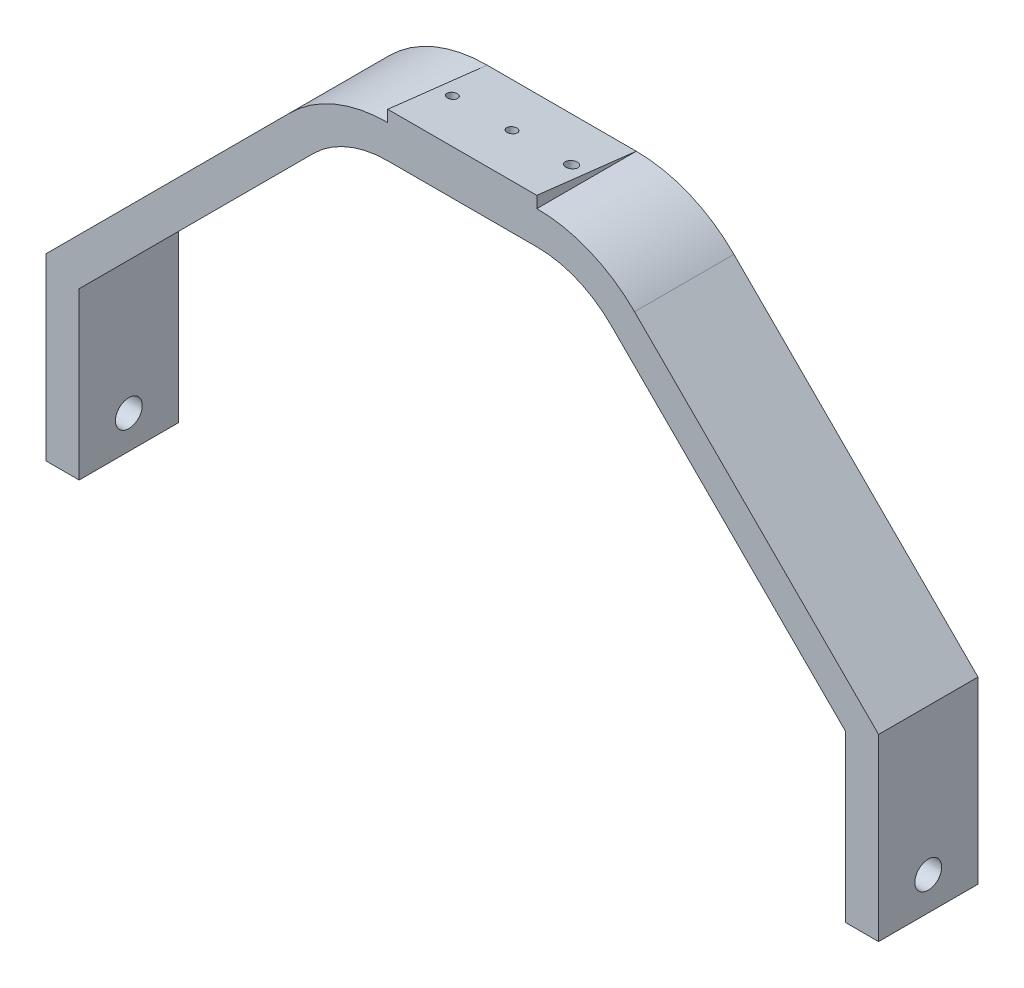
SolidWorks part; units mm, degrees
ref_plane "Alzado" through (0, 0, 0) normal (0, 0, 1) x (1, 0, 0)
ref_plane "Planta" through (0, 0, 0) normal (0, 1, 0) x (1, 0, 0)
ref_plane "Vista lateral" through (0, 0, 0) normal (1, 0, 0) x (0, 0, -1)
sketch "Croquis1" plane through (0, 0, 0) normal (0, 0, 1) x (1, 0, 0)
  line L0 (-22.5, -36.6894) -> (-68.1161, -36.6894) construction
  line L1 (-22.5, -5) -> (22.5, -5)
  line L3 (-22.5, 5) -> (22.5, 5)
  line L5 (0, -5) -> (0, 9.8205) construction
  line L6 (-51.9789, -7.2106) -> (-122.6896, -77.9212)
  line L7 (-68.1161, -36.6894) -> (22.5, -36.6894) construction
  line L8 (-22.5, -36.6894) -> (-55.2569, -3.9326) construction
  line L9 (-44.9078, -14.2816) -> (-115.6185, -84.9923)
  line L12 (-115.6185, -84.9923) -> (-115.6185, -134.9923)
  line L14 (22.5, -36.6894) -> (55.2569, -3.9326) construction
  line L15 (68.1161, -36.6894) -> (-22.5, -36.6894) construction
  line L16 (22.5, -36.6894) -> (68.1161, -36.6894) construction
  line L23 (-115.6185, -134.9923) -> (-125.6185, -134.9923)
  line L24 (-125.6185, -134.9923) -> (-125.6185, -80.8502)
  line L25 (-122.6896, -77.9212) -> (-125.6185, -80.8502)
  line L26 (44.9078, -14.2816) -> (115.6185, -84.9923)
  line L27 (51.9789, -7.2106) -> (122.6896, -77.9212)
  line L28 (122.6896, -77.9212) -> (125.6185, -80.8502)
  line L29 (125.6185, -134.9923) -> (125.6185, -80.8502)
  line L30 (115.6185, -134.9923) -> (125.6185, -134.9923)
  line L31 (115.6185, -84.9923) -> (115.6185, -134.9923)
  arc A0 (-22.5, -5) -> (-44.9078, -14.2816) centre (-22.5, -36.6894) ccw
  arc A1 (-22.5, 5) -> (-51.9789, -7.2106) centre (-22.5, -36.6894) ccw
  arc A2 (22.5, 5) -> (51.9789, -7.2106) centre (22.5, -36.6894) cw
  arc A3 (22.5, -5) -> (44.9078, -14.2816) centre (22.5, -36.6894) cw
  point P0 (0, 0)
extrude "Saliente-Extruir1" add sketch "Croquis1" along normal blind 30
sketch "Croquis3" plane through (-125.6185, 0, 0) normal (-1, 0, 0) x (0, 0, 1)
  line L0 (30, -134.9923) -> (0, -134.9923) construction
  circle A0 centre (15, -124.9923) radius 4.05
  dimension "D1" = 10
  dimension "D2" = 8.1
extrude "Cortar-Extruir1" cut sketch "Croquis3" against normal through all
sketch "Croquis4" plane through (0, 5, 0) normal (0, 1, 0) x (1, 0, 0)
  circle A1 centre (0, -15) radius 1.5
  circle A3 centre (18, -15) radius 1.5
  circle A4 centre (-18, -15) radius 1.5
  point P9 (0, -15)
extrude "Cortar-Extruir2" cut sketch "Croquis4" against normal through all
sketch "Croquis5" plane through (0, 5, 0) normal (0, 1, 0) x (1, 0, 0)
  line L1 (-22.5, 0) -> (22.5, 0)
  line L2 (-22.5, 0) -> (-22.5, -30)
  line L3 (-22.5, -30) -> (22.5, -30)
  line L4 (22.5, 0) -> (22.5, -30)
extrude "Saliente-Extruir2" add sketch "Croquis5" along normal blind 12
sketch "Croquis6" plane through (22.5, 0, 0) normal (1, 0, 0) x (0, 0, -1)
  line L0 (0, 5) -> (-30, 8.4711)
  line L1 (-30, 17) -> (-30, 5) construction
  line L4 (-30, 8.4711) -> (-30, 19.9231)
  line L5 (-30, 19.9231) -> (0, 19.9231)
  line L6 (0, 19.9231) -> (0, 5)
extrude "Cortar-Extruir3" cut sketch "Croquis6" against normal through all
sketch "Croquis7" plane through (0, -5, 0) normal (0, -1, 0) x (1, 0, 0)
sketch "Croquis8" plane through (0, -5, 0) normal (0, -1, 0) x (1, 0, 0)
  circle A0 centre (0, 15) radius 1.5
  circle A1 centre (-18, 15) radius 1.5
  circle A2 centre (18, 15) radius 1.5
extrude "Saliente-Extruir3" add sketch "Croquis8" against normal through all
sketch "Croquis9" plane through (0, 4.9339, -0.5709) normal (0, 0.9934, -0.1149) x (1, 0, 0)
  line L1 (-22.5, -0.5747) -> (22.5, -0.5747)
  line L2 (-22.5, -0.5747) -> (-22.5, -30.7748)
  line L3 (-22.5, -30.7748) -> (22.5, -30.7748)
  line L4 (22.5, -0.5747) -> (22.5, -30.7748)
extrude "Cortar-Extruir5" cut sketch "Croquis9" along normal blind 10
sketch "Croquis10" plane through (0, 4.9339, -0.5709) normal (0, 0.9934, -0.1149) x (1, 0, 0)
  circle A0 centre (0, -15.6748) radius 1.5
  circle A1 centre (-18, -15.6748) radius 1.5
  circle A2 centre (18, -15.6748) radius 1.735
  point P5 (0, -15.6748)
extrude "Cortar-Extruir6" cut sketch "Croquis10" against normal blind 18
